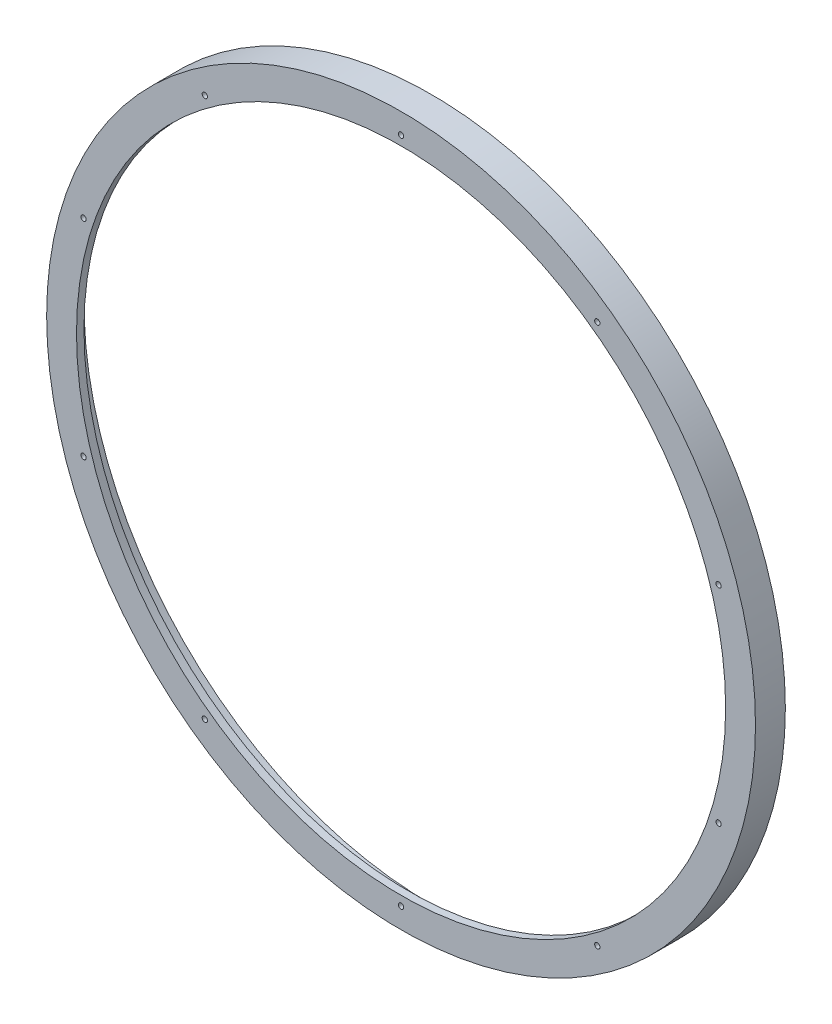
SolidWorks part; units mm, degrees
material "6061 Alloy"
ref_plane "Front Plane" through (0, 0, 0) normal (0, 0, 1) x (1, 0, 0)
ref_plane "Top Plane" through (0, 0, 0) normal (0, 1, 0) x (1, 0, 0)
ref_plane "Right Plane" through (0, 0, 0) normal (1, 0, 0) x (0, 0, -1)
sketch "Sketch1" plane through (0, 0, 0) normal (1, 0, 0) x (0, 0, -1)
  line L0 (3.175, 147.574) -> (12.7, 147.574)
  line L1 (12.7, 147.574) -> (12.7, 150.749)
  line L2 (12.7, 150.749) -> (0, 150.749)
  line L3 (0, 150.749) -> (0, 138.049)
  line L4 (0, 138.049) -> (3.175, 138.049)
  line L5 (3.175, 138.049) -> (3.175, 147.574)
  line L6 (0, 0) -> (50000, 0) construction
  dimension "D1" = 3.175
  dimension "D2" = 3.175
  dimension "D3" = 301.498
  dimension "D4" = 12.7
  dimension "D5" = 12.7
revolve "Revolve1" add sketch "Sketch1" angle 360 about L6
hole_wizard "#4-40 Tapped Hole1" positions "Sketch3" profile "Sketch4" tap size "#4-40" standard "Ansi Inch" end condition through all
sketch "Sketch3" plane through (0, 0, 0) normal (0, 0, 1) x (1, 0, 0)
  point P1 (0, 142)
  dimension "D1" = 142
sketch "Sketch4" plane through (0, 142, 0) normal (1, 0, 0) x (0, -1, 0)
  line L0 (0, 0) -> (0, 12.7)
  line L1 (0, 12.7) -> (1.1303, 12.7)
  line L2 (1.1303, 12.7) -> (1.1303, 0)
  line L5 (1.1303, 0) -> (0, 0)
  line L11 (0, -6.35) -> (0, 107.95) construction
  dimension "Thru Tap Drill Dia." = 2.2606
  dimension "Thru Tap Drill Depth" = 12.7
cosmetic thread "Hole Thread1" parameters "D2"=2.8448
pattern_circular "CirPattern1" count 10 over 360 about axis through (0, 0, 0) along (0, 0, 1) of "#4-40 Tapped Hole1"
